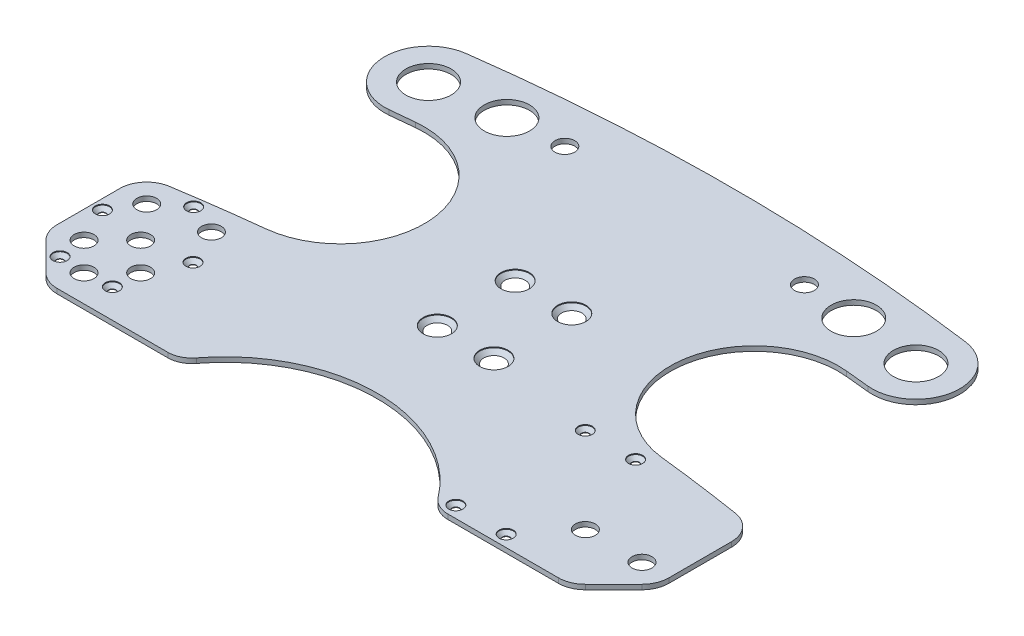
SolidWorks part; units mm, degrees
ref_plane "Front Plane" through (0, 0, 0) normal (0, 0, 1) x (1, 0, 0)
ref_plane "Top Plane" through (0, 0, 0) normal (0, 1, 0) x (1, 0, 0)
ref_plane "Right Plane" through (0, 0, 0) normal (1, 0, 0) x (0, 0, -1)
sketch "Sketch1" plane through (0, 0, 0) normal (0, 1, 0) x (1, 0, 0)
  line L1 (-120, -95) -> (120, -95)
  line L2 (-120, -95) -> (-120, 95)
  line L3 (-120, 95) -> (120, 95)
  line L4 (120, -95) -> (120, 95)
  line L5 (-120, -95) -> (120, 95) construction
  line L6 (-120, 95) -> (120, -95) construction
  line L7 (-10, 13.75) -> (10, 13.75)
  line L8 (-10, 13.75) -> (-10, -13.75)
  line L9 (-10, -13.75) -> (10, -13.75)
  line L10 (10, 13.75) -> (10, -13.75)
  line L11 (-10, 13.75) -> (10, -13.75) construction
  line L12 (-10, -13.75) -> (10, 13.75) construction
  circle A0 centre (0, 0) radius 95
  circle A1 centre (-10, 13.75) radius 2.5
  circle A2 centre (10, 13.75) radius 2.5
  circle A3 centre (10, -13.75) radius 2.5
  circle A4 centre (-10, -13.75) radius 2.5
  circle A5 centre (0, 0) radius 120
  dimension "D3" = 5
  dimension "D1" = 240
  dimension "D2" = 190
  dimension "D4" = 27.5
  dimension "D5" = 20
extrude "Boss-Extrude1" add sketch "Sketch1" along normal blind 1.7 contours A0 A4 L8 A1 L7 A2 L10 A3 L9 | A4 L9 A3 L10 A2 L7 A1 L8 | L3 A5 L1 A0 | L1 A5 L3 A0 region at (-105.6812, 0, 51.9346) region at (68.7642, 0, 68.7642) region at (-92.313, 0, 0) region at (0, 0, 0)
sketch "Sketch2" plane through (0, 1.7, 0) normal (0, 1, 0) x (1, 0, 0)
  line L0 (-81.1673, -40) -> (21.9115, -40) construction
  line L1 (-127.3056, -60) -> (138.909, -60) construction
  line L2 (-88.5406, 28.139) -> (-88.5406, -89.0376) construction
  line L3 (-88.5406, -40) -> (-88.5406, -60) construction
  line L4 (0, 21.6044) -> (0, -21.4213) construction
  line L5 (88.5406, 33.139) -> (88.5406, -84.0376) construction
  line L6 (-151.9803, -25) -> (55.006, -25) construction
  line L7 (-48.8837, 35) -> (62.426, 35) construction
  circle A0 centre (0, 0) radius 35
  circle A1 centre (0, 35) radius 2.5
  circle A2 centre (30.3109, 17.5) radius 2.5
  circle A3 centre (30.3109, -17.5) radius 2.5
  circle A4 centre (0, -35) radius 2.5
  circle A5 centre (-30.3109, -17.5) radius 2.5
  circle A6 centre (-30.3109, 17.5) radius 2.5
  circle A7 centre (-88.5406, -40) radius 3.5
  circle A8 centre (-88.5406, -50) radius 10
  circle A9 centre (-78.5406, -50) radius 3.5
  circle A10 centre (-88.5406, -60) radius 3.5
  circle A11 centre (-98.5406, -50) radius 3.5
  circle A12 centre (78.5406, -50) radius 3.5
  circle A13 centre (98.5406, -50) radius 3.5
  circle A14 centre (-98.5406, -27.8625) radius 3.5
  circle A15 centre (-78.5406, -25) radius 3.5
  circle A16 centre (0, 0) radius 45
  circle A17 centre (0, -580) radius 625
  circle A18 centre (0, -580) radius 645
  circle A19 centre (-86.0945, 59.2282) radius 8
  circle A20 centre (-61.2596, 62.0843) radius 8
  circle A21 centre (-86.0945, 59.2282) radius 15.5
  arc A22 (-73.3144, 95) -> (-73.3144, -95) centre (0, 0) ccw construction
  circle A23 centre (-61.2596, 62.0843) radius 9.5
  circle A24 centre (-86.0945, 59.2282) radius 9.5
  circle A25 centre (61.2596, 62.0843) radius 8
  circle A26 centre (86.0945, 59.2282) radius 8
  circle A27 centre (-42.3209, 63.6101) radius 3.5
  circle A28 centre (0, 0) radius 70
  circle A29 centre (42.3209, 63.6101) radius 3.5
  circle A30 centre (-98.5406, -50) radius 9.5
  circle A31 centre (42.3209, 63.6101) radius 9.5
  circle A32 centre (61.2596, 62.0843) radius 9.5
  circle A33 centre (0, -645.0455) radius 625
  point P17 (0, 0)
  point P21 (-88.5406, -50)
  point P37 (-88.5406, -50)
  point P56 (0, 65)
  point P57 (0, 45)
  point P68 (-76.6704, 60.4269)
  point P69 (-70.7097, 61.1124)
  point P81 (0, 0)
  point P85 (-98.5406, -27.8625)
  dimension "D1" = 70
  dimension "D2" = 5
  dimension "D4" = 7
  dimension "D9" = 90
  dimension "D10" = 1250
  dimension "D11" = 20
  dimension "D12" = 16
  dimension "D14" = 6
  dimension "D13" = 19
  dimension "D17" = 140
  dimension "D18" = 6
  dimension "D5" = 20
  dimension "D6" = 40
  dimension "D8" = 15
  dimension "D15" = 6
  dimension "D3" = 6
  dimension "D7" = 4
extrude "Cut-Extrude1" cut sketch "Sketch2" against normal up to next contours A7 | A9 | A10 | A11 | A12 | A13 | A14 | A15 | A19 | A20 | A25 | A26 | A27 | A29
sketch "Sketch3" plane through (0, 1.7, 0) normal (0, 1, 0) x (1, 0, 0)
  line L1 (-84.5506, 43.8053) -> (-40.7771, 48.1872)
  line L2 (0, 100.6986) -> (0, -98.8678) construction
  line L3 (-10.3445, 0) -> (20.4144, 0) construction
  line L5 (84.5506, 43.8053) -> (40.7771, 48.1872)
  line L6 (-42.3209, 63.6101) -> (0, 0) construction
  line L7 (-36.306, 26.5871) -> (-55.2257, 55.0243)
  line L8 (-10.4964, 43.7587) -> (-29.4161, 72.1959)
  line L9 (10.4964, 43.7587) -> (29.4161, 72.1959)
  line L10 (36.306, 26.5871) -> (55.2257, 55.0243)
  line L11 (-108.0406, -50) -> (-108.0406, -27.8625)
  line L13 (-73.3144, -95) -> (73.3144, -95)
  line L14 (73.3144, 95) -> (-73.3144, 95)
  line L15 (-73.3144, -95) -> (73.3144, -95)
  line L16 (73.3144, 95) -> (-73.3144, 95)
  line L17 (-69.0406, -25) -> (-69.0406, -50)
  line L18 (-71.8231, -56.7175) -> (-81.8231, -66.7175)
  line L19 (-105.2581, -56.7175) -> (-95.2581, -66.7175)
  line L20 (-42.3209, 79.1101) -> (42.3209, 79.1101)
  line L21 (-78.5406, -15.5) -> (-42.2463, -15.5)
  line L22 (0, -45) -> (111.243, -45) construction
  line L23 (-88.5406, -69.5) -> (88.5406, -69.5)
  line L24 (69.0406, -15.5) -> (45.0406, -15.5)
  line L25 (78.5406, -15.5) -> (42.2463, -15.5)
  line L27 (108.0406, -50) -> (108.0406, -27.8625)
  line L28 (105.2581, -56.7175) -> (95.2581, -66.7175)
  line L29 (69.0406, -15.5) -> (69.0406, -69.5)
  line L30 (69.0406, -69.5) -> (45.0406, -69.5)
  line L31 (45.0406, -15.5) -> (45.0406, -69.5)
  line L32 (57.0406, -15.5) -> (57.0406, -69.5) construction
  line L33 (45.0406, -42.5) -> (69.0406, -42.5) construction
  circle A0 centre (-86.0945, 59.2282) radius 15.5
  arc A1 (-73.3144, 95) -> (-73.3144, -95) centre (0, 0) ccw construction
  circle A2 centre (-42.3209, 63.6101) radius 15.5
  circle A3 centre (86.0945, 59.2282) radius 15.5
  circle A4 centre (42.3209, 63.6101) radius 15.5
  circle A5 centre (0, 0) radius 45
  circle A6 centre (-98.5406, -27.8625) radius 9.5
  circle A7 centre (-98.5406, -27.8625) radius 3.5 construction
  arc A8 (-73.3144, 95) -> (-73.3144, -95) centre (0, 0) ccw
  arc A9 (73.3144, -95) -> (73.3144, 95) centre (0, 0) ccw
  arc A10 (-73.3144, 95) -> (-73.3144, -95) centre (0, 0) ccw
  arc A11 (73.3144, -95) -> (73.3144, 95) centre (0, 0) ccw
  circle A12 centre (-78.5406, -25) radius 9.5
  circle A13 centre (-88.5406, -60) radius 9.5
  circle A14 centre (-98.5406, -50) radius 9.5
  circle A15 centre (-78.5406, -50) radius 9.5
  circle A17 centre (98.5406, -50) radius 9.5
  circle A18 centre (78.5406, -50) radius 9.5
  arc A19 (73.3144, -95) -> (73.3144, 95) centre (0, 0) ccw construction
  arc A20 (-45.0406, -69.5) -> (45.0406, -69.5) centre (0, -98.6511) cw
  circle A21 centre (98.5406, -27.8625) radius 9.5
  circle A22 centre (98.5406, -50) radius 9.5
  circle A23 centre (88.5406, -60) radius 9.5
  circle A24 centre (-73.1485, 15.1063) radius 29.692
  circle A25 centre (73.1485, 15.1063) radius 29.692
  circle A26 centre (48.1506, -19.64) radius 1.3
  circle A27 centre (65.9306, -19.64) radius 1.3
  circle A28 centre (65.9306, -65.36) radius 1.3
  circle A29 centre (48.1506, -65.36) radius 1.3
  circle A30 centre (0, -580) radius 645
  circle A31 centre (0, -580) radius 660.5
  circle A32 centre (0, -645.0455) radius 634.5
  point P20 (0, -659.5242)
  arc M45 (-73.3144, 95) -> (-73.3144, -95) centre (0, 0) ccw
  line M46 (-73.3144, -95) -> (73.3144, -95)
  arc M47 (73.3144, -95) -> (73.3144, 95) centre (0, 0) ccw
  line M48 (73.3144, 95) -> (-73.3144, 95)
  dimension "D1" = 90
  dimension "D3" = 6
  dimension "D5" = 2.6
  dimension "D4" = 24
  dimension "D6" = 17.78
  dimension "D7" = 45.72
  dimension "D2" = 0
extrude "Cut-Extrude2" cut sketch "Sketch3" against normal up to next contours A24 L1 A0 A14 L11 A6 L21 M45 | A24 | L28 A23 L23 A13 L19 A14 A10 A17 M46 M47 | A20 L23 | L5 A25 L24 L25 A21 L27 A17 A11 A3 | A25 | A30 A0 M45 | A31 A11 M48 M45 | A0 A31 A10 | A31 A3 M47 | A30 A3 M47 | A6 A32 A14 L11 M45 | A11 A32 A21 L27 A17 | A26 | A27 | A28 | A29 region at (-105.8887, 1.7, -12.959) region at (-73.1485, 1.7, -15.1063) region at (-102.839, 1.7, -59.5932) region at (-94.2652, 1.7, -72.7135) region at (0, 1.7, -86.2332) region at (-111.2756, 1.7, 31.2797) region at (0, 1.7, 81.3426) region at (0, 1.7, 59.4787) region at (73.1485, 1.7, -15.1063) region at (105.8887, 1.7, -12.959) region at (111.2756, 1.7, 31.2797) region at (94.2652, 1.7, -72.7135) region at (102.839, 1.7, -59.5932)
fillet "Fillet1" radius 8.5 2 edges at (45.0406, 0.85, 69.5) (-45.0406, 0.85, 69.5)
sketch "Sketch8" plane through (0, 1.7, 0) normal (0, 1, 0) x (1, 0, 0)
  circle A8 centre (-89.4023, -20.411) radius 1.25
  circle A9 centre (-104.5406, -37.5) radius 1.25
  circle A10 centre (-72.5406, -37.5) radius 1.25
  circle A11 centre (-97.7832, -59.2426) radius 1.25
  circle A17 centre (-79.298, -59.2426) radius 1.25
  circle A19 centre (-89.4023, -20.411) radius 1.5 construction
  circle A20 centre (-104.5406, -37.5) radius 1.5 construction
  circle A21 centre (-72.5406, -37.5) radius 1.5 construction
  circle A22 centre (-79.298, -59.2426) radius 1.5 construction
  circle A23 centre (-97.7832, -59.2426) radius 1.5 construction
  dimension "D1" = 2.5
extrude "Cut-Extrude3" cut sketch "Sketch8" against normal up to next contours A8 | A10 | A9 | A11 | A17
hole_wizard "CSK for M5 Flat Head Machine Screw1" positions "Sketch4" profile "Sketch5" countersink size "M5" standard "ANSI Metric"
sketch "Sketch4" plane through (0, 1.7, 0) normal (0, 1, 0) x (1, 0, 0)
  point P0 (-10, 13.75)
  point P3 (10, 13.75)
  point P6 (10, -13.75)
  point P9 (-10, -13.75)
sketch "Sketch5" plane through (-10, 1.7, -13.75) normal (1, 0, 0) x (0, 0, 1)
  line L0 (0, 0) -> (0, 6.5022)
  line L1 (0, 6.5022) -> (2.5, 5)
  line L2 (2.5, 5) -> (2.5, 2.8)
  line L3 (2.5, 2.8) -> (5, 0.3)
  line L4 (5, 0.3) -> (5, 0)
  line L6 (5, 0) -> (0, 0)
  line L7 (-2.5, 2.8) -> (-5, 0.3) construction
  line L10 (0, 6.5022) -> (-2.5, 5) construction
  line L11 (0, -6.35) -> (0, 107.95) construction
  dimension "Hole Dia." = 5
  dimension "Hole Depth" = 5
  dimension "C'Sink Dia." = 10
  dimension "C'Sink Angle" = 90
  dimension "Drill Angle" = 118
  dimension "Head Clearance" = 0.3
hole_wizard "CSK for M2.5 Flat Head Machine Screw1" positions "Sketch6" profile "Sketch7" countersink size "M2.5" standard "ANSI Metric"
sketch "Sketch6" plane through (0, 1.7, 0) normal (0, 1, 0) x (1, 0, 0)
  point P0 (48.1506, -19.64)
  point P3 (65.9306, -19.64)
  point P6 (65.9306, -65.36)
  point P9 (48.1506, -65.36)
  point P12 (-89.4023, -20.411)
  point P15 (-72.5406, -37.5)
  point P18 (-104.5406, -37.5)
  point P21 (-97.7832, -59.2426)
  point P24 (-79.298, -59.2426)
sketch "Sketch7" plane through (48.1506, 1.7, 19.64) normal (1, 0, 0) x (0, 0, 1)
  line L0 (0, 0) -> (0, 5.7511)
  line L1 (0, 5.7511) -> (1.25, 5)
  line L2 (1.25, 5) -> (1.25, 1.55)
  line L3 (1.25, 1.55) -> (2.5, 0.3)
  line L4 (2.5, 0.3) -> (2.5, 0)
  line L6 (2.5, 0) -> (0, 0)
  line L7 (-1.25, 1.55) -> (-2.5, 0.3) construction
  line L10 (0, 5.7511) -> (-1.25, 5) construction
  line L11 (0, -6.35) -> (0, 107.95) construction
  dimension "Hole Dia." = 2.5
  dimension "Hole Depth" = 5
  dimension "C'Sink Dia." = 5
  dimension "C'Sink Angle" = 90
  dimension "Drill Angle" = 118
  dimension "Head Clearance" = 0.3
